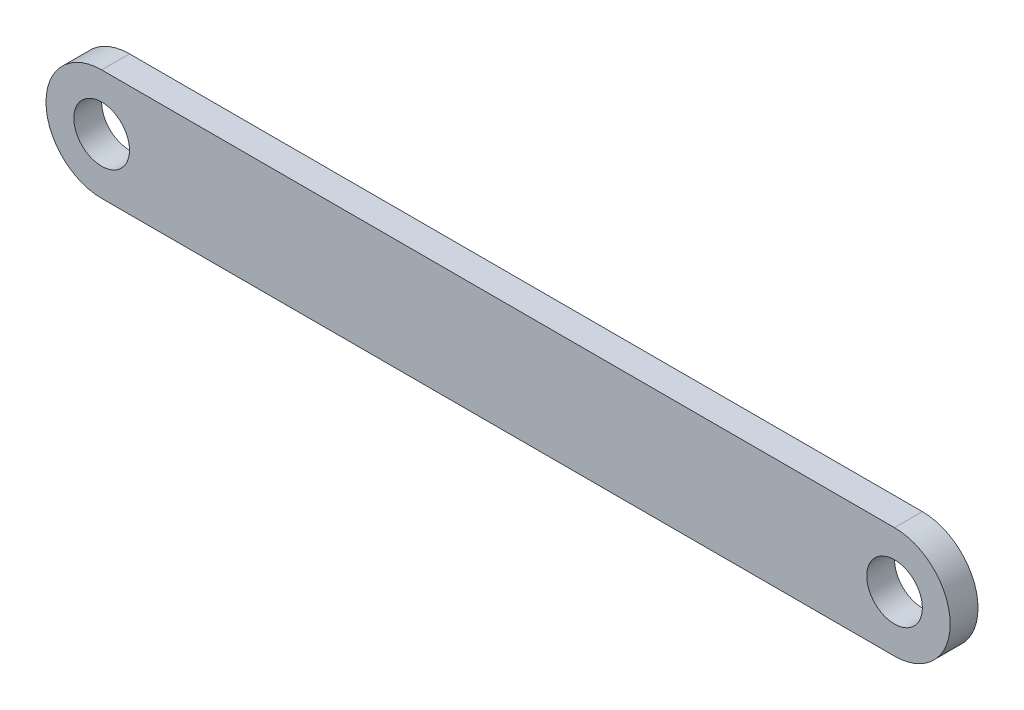
SolidWorks part; units mm, degrees
ref_plane "Спереди" through (0, 0, 0) normal (0, 0, 1) x (1, 0, 0)
ref_plane "Сверху" through (0, 0, 0) normal (0, 1, 0) x (1, 0, 0)
ref_plane "Справа" through (0, 0, 0) normal (1, 0, 0) x (0, 0, -1)
sketch "Эскиз1" plane through (0, 0, 0) normal (0, 0, 1) x (1, 0, 0)
  line L0 (0, 0) -> (-28.5003, 0)
  line L1 (-28.5003, -2) -> (0, -2)
  line L2 (-28.5003, 2) -> (0, 2)
  circle A0 centre (-28.5003, 0) radius 1
  circle A1 centre (0, 0) radius 1
  circle A2 centre (-28.5003, 0) radius 2
  circle A3 centre (0, 0) radius 2
  dimension "D1" = 28.5003
extrude "Бобышка-Вытянуть1" add sketch "Эскиз1" along normal mid plane 1 contours A3 L2 A2 L0 | A3 L0 A2 L1 | A2 A0 | A3 A1 region at (-14.2502, 1.0187, 0) region at (-27.1261, -1.3742, 0) region at (-14.2501, -1.0187, 0) region at (-1.3742, 1.3742, 0)
sketch "Sketch1" plane through (0, 0, 0) normal (0, 0, 1) x (1, 0, 0)
  line L0 (0, 0) -> (-14, 0)
  line L1 (-14, 0) -> (-14, 1.5)
  line L2 (-25.5979, -2) -> (-2.0642, -2)
  line L3 (-14, 0) -> (-28.5003, 0)
  line L7 (-14, 1.5) -> (-20.4712, -4.9712)
  line L11 (0, 2) -> (-30.8022, 2)
  line L12 (-14, 1.5) -> (-7.5288, -4.9712)
  line L13 (-20.4712, -4.9712) -> (-7.5288, -4.9712)
  line L14 (-15.6569, 5.5) -> (-30.1281, -8.9712)
  line L15 (-30.1281, -8.9712) -> (2.1281, -8.9712)
  line L16 (-12.3431, 5.5) -> (2.1281, -8.9712)
  line L17 (-14, 1.5) -> (-14, 5.5)
  line L18 (-14, 5.5) -> (-15.6569, 5.5)
  line L19 (-14, 5.5) -> (-12.3431, 5.5)
  line L21 (-14, 7.1569) -> (-30.1281, -8.9712) construction
  line L22 (-14, 7.1569) -> (2.1281, -8.9712) construction
  point P6 (-9.7278, -2.9956)
  point P9 (-14.7071, 0.7071)
  point P10 (-13.2929, 0.7071)
  point P11 (-21.4142, -2.5858)
  point P15 (-16, 0)
  point P22 (-10, 0)
  dimension "D1" = 4
  dimension "D4" = 14
  dimension "D2" = 1.5
